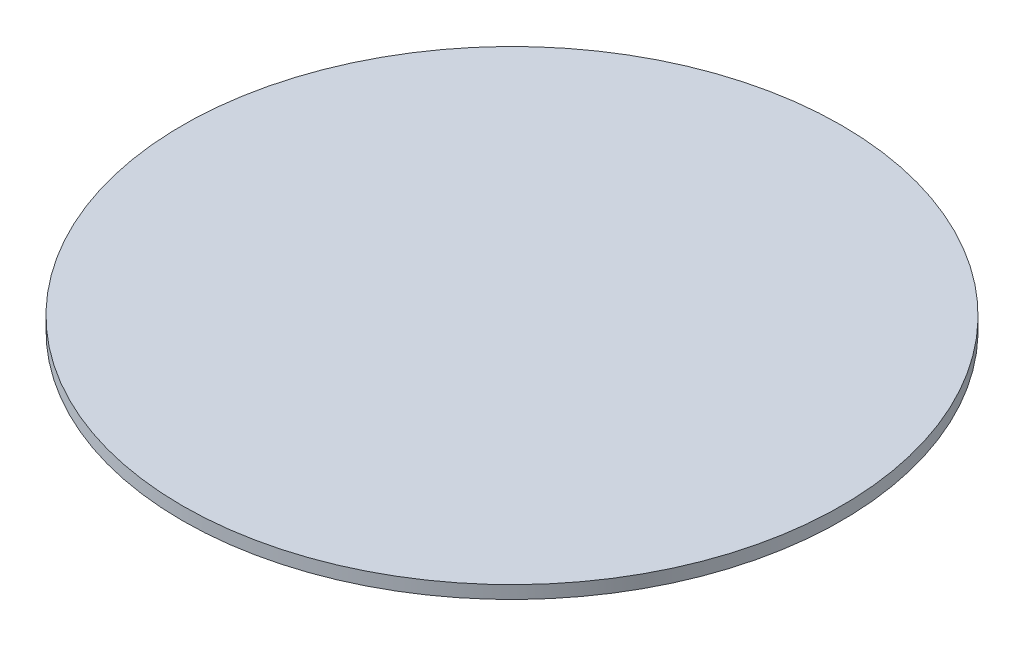
SolidWorks part; units mm, degrees
ref_plane "Front" through (0, 0, 0) normal (0, 0, 1) x (1, 0, 0)
ref_plane "Top" through (0, 0, 0) normal (0, 1, 0) x (1, 0, 0)
ref_plane "Right" through (0, 0, 0) normal (1, 0, 0) x (0, 0, -1)
sketch "Sketch1" plane through (0, 0, 0) normal (0, 1, 0) x (1, 0, 0)
  circle A0 centre (0, 0) radius 25.5761
  dimension "D1" = 51.1522
extrude "Boss-Extrude1" add sketch "Sketch1" along normal blind 1
ref_axis "Axis1" through (0, 9.6422, 0) along (0, -1, 0)
